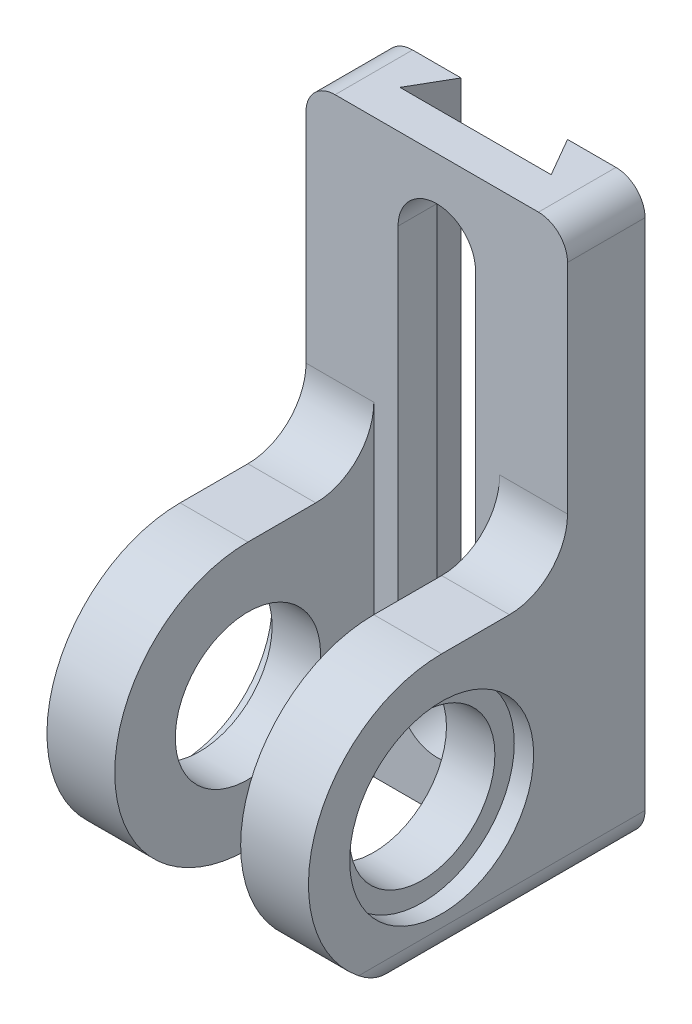
SolidWorks part; units mm, degrees
material "1060 Alloy"
ref_plane "Front Plane" through (0, 0, 0) normal (1, 0, 0) x (0, 1, 0)
ref_plane "Top Plane" through (0, 0, 0) normal (0, 0, 1) x (0, 1, 0)
ref_plane "Right Plane" through (0, 0, 0) normal (0, 1, 0) x (-1, 0, 0)
sketch "Sketch1" plane through (0, 0, 0) normal (1, 0, 0) x (0, 1, 0)
  line L0 (0, 0) -> (0, 42)
  line L1 (55, 42) -> (55, 28)
  line L2 (67, 16) -> (118, 16)
  line L3 (118, 16) -> (118, 0)
  line L4 (118, 0) -> (0, 0)
  arc A0 (0, 42) -> (55, 42) centre (27.5, 42) cw
  arc A1 (55, 28) -> (67, 16) centre (67, 28) ccw
  dimension "D2" = 27.5
  dimension "D4" = 12
  dimension "D1" = 42
  dimension "D3" = 16
  dimension "D5" = 118
extrude "Boss-Extrude1" add sketch "Sketch1" against normal blind 27
sketch "Sketch3" plane through (0, 0, 0) normal (1, 0, 0) x (0, 1, 0)
  line L0 (0, 42) -> (27.5, 42) construction
  point P1 (27.5, 42)
  dimension "D1" = 27.5
hole_wizard "CBORE for M5 Hex Head Bolt1" positions "Sketch3" profile "Sketch4" counterbore size "M5" standard "ANSI Metric" end condition through all
sketch "Sketch4" plane through (0, 27.5, 42) normal (0, 1, 0) x (0, 0, -1)
  line L0 (0, 0) -> (0, 27)
  line L1 (0, 27) -> (15, 27)
  line L3 (15, 27) -> (15, 4)
  line L4 (15, 4) -> (19, 4)
  line L5 (19, 4) -> (19, 0)
  line L7 (19, 0) -> (0, 0)
  line L11 (0, -6.35) -> (0, 107.95) construction
  dimension "Thru Hole Dia." = 30
  dimension "Thru Hole Depth" = 27
  dimension "C'Bore Dia." = 38
  dimension "C'Bore Depth" = 4
sketch "Sketch5" plane through (0, 0, 0) normal (0, -1, 0) x (1, 0, 0)
  line L0 (-27, 69.5) -> (-14, 69.5)
  line L3 (-14, 16) -> (-27, 16)
  line L5 (-27, 16) -> (-27, 69.5)
  line L6 (-14, 69.5) -> (-14, 16)
  point P8 (-13.5, 15.2903)
  point P9 (0, 0)
  dimension "D2" = 16
  dimension "D1" = 13
extrude "Cut-Extrude2" cut sketch "Sketch5" against normal through all
sketch "Sketch6" plane through (0, 0, 0) normal (0, -1, 0) x (1, 0, 0)
  line L0 (-16, 0) -> (-11.3812, 8)
  line L1 (-27, 0) -> (0, 0) construction
  line L2 (-11.3812, 8) -> (-27, 8)
  line L3 (-27, 16) -> (-27, 0) construction
  dimension "D1" = 60
  dimension "D2" = 8
  dimension "D3" = 16
extrude "Cut-Extrude3" cut sketch "Sketch6" against normal through all and the other way through all
mirror "Mirror1" about plane through (-27, 27.5, 42) normal (-1, 0, 0) of bodies 105
sketch "Sketch7" plane through (0, 0, 16) normal (0, 0, 1) x (1, 0, 0)
  line L0 (-27, 101) -> (-27, 18) construction
  line L1 (-19, 101) -> (-19, 18)
  line L2 (-35, 101) -> (-35, 18)
  line L4 (0, 118) -> (0, 67) construction
  line L5 (-54, 118) -> (0, 118) construction
  line L6 (-40, 0) -> (-14, 0) construction
  arc A0 (-19, 101) -> (-35, 101) centre (-27, 101) ccw
  arc A1 (-35, 18) -> (-19, 18) centre (-27, 18) ccw
  point P2 (-27, 59.5)
  point P9 (-27, 109)
  point P14 (-27, 0)
  point P17 (-28.0364, -1.2868)
  point P18 (-28.1418, 108.1352)
  dimension "D2" = 9
  dimension "D3" = 99
  dimension "D1" = 19
  dimension "D4" = 16
extrude "Cut-Extrude4" cut sketch "Sketch7" against normal through all
fillet "Fillet1" radius 6 1 edges at (0, 0, 21) tangent propagation no
fillet "Fillet2" radius 6 3 edges at (0, 118, 8) (-54, 118, 8) (-54, 0, 21) tangent propagation no
sketch "Sketch9" plane through (0, 0, 0) normal (0, -1, 0) x (1, 0, 0)
